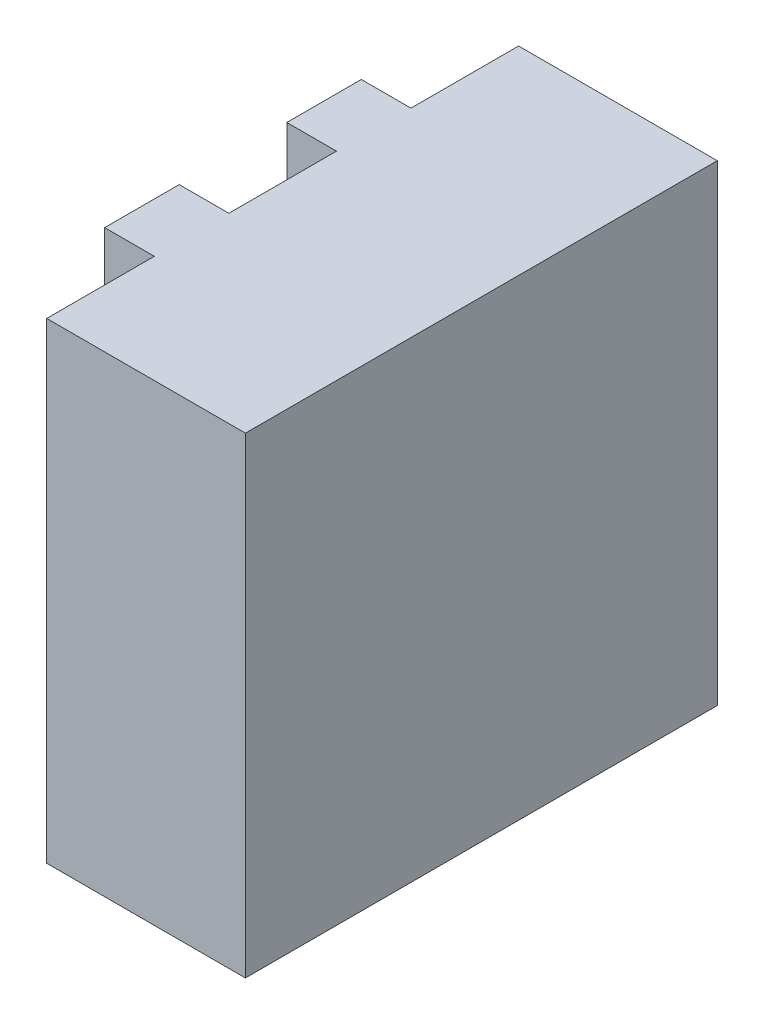
SolidWorks part; units mm, degrees
ref_plane "前视基准面" through (0, 0, 0) normal (0, 0, 1) x (1, 0, 0)
ref_plane "上视基准面" through (0, 0, 0) normal (0, 1, 0) x (1, 0, 0)
ref_plane "右视基准面" through (0, 0, 0) normal (1, 0, 0) x (0, 0, -1)
other "Configuration Table"
sketch "草图1" plane through (0, 0, 0) normal (1, 0, 0) x (0, 0, -1)
  line L0 (9.5, 7.7151) -> (7.3333, 7.7151) construction
  line L9 (0, 0) -> (9.5, 0)
  line L10 (0, 0) -> (0, 9.5)
  line L11 (0, 9.5) -> (9.5, 9.5)
  line L12 (9.5, 0) -> (9.5, 9.5)
  line L13 (7.3333, 9.5) -> (5.8333, 9.5)
  line L14 (7.3333, 9.5) -> (7.3333, 1.5)
  line L15 (7.3333, 1.5) -> (5.8333, 1.5)
  line L16 (5.8333, 9.5) -> (5.8333, 1.5)
  line L17 (3.6667, 9.5) -> (2.1667, 9.5)
  line L18 (3.6667, 9.5) -> (3.6667, 1.5)
  line L19 (3.6667, 1.5) -> (2.1667, 1.5)
  line L20 (2.1667, 9.5) -> (2.1667, 1.5)
  line L21 (5.8333, 7.7151) -> (3.6667, 7.7151) construction
  line L22 (2.1667, 7.7151) -> (0, 7.7151) construction
  line L23 (7.3333, 1.5) -> (7.3333, 0)
  line L24 (7.0833, 0.9) -> (6.0833, 0.9)
  line L25 (7.0833, 0.9) -> (7.0833, 0.6)
  line L26 (7.0833, 0.6) -> (6.0833, 0.6)
  line L27 (6.0833, 0.9) -> (6.0833, 0.6)
  line L28 (6.7333, 0.25) -> (6.4333, 0.25)
  line L29 (6.7333, 0.25) -> (6.7333, 1.25)
  line L30 (6.7333, 1.25) -> (6.4333, 1.25)
  line L31 (6.4333, 0.25) -> (6.4333, 1.25)
  line L33 (2.4167, 0.9) -> (3.4167, 0.9)
  line L34 (2.4167, 0.9) -> (2.4167, 0.6)
  line L35 (2.4167, 0.6) -> (3.4167, 0.6)
  line L36 (3.4167, 0.9) -> (3.4167, 0.6)
  point P28 (6.5833, 1.25)
  point P29 (6.5833, 1.5)
  point P30 (7.0833, 0.75)
  point P31 (6.7333, 0.75)
  point P32 (6.5833, 0.9)
  point P33 (7.3333, 0.75)
  point P39 (2.9167, 0.9)
  point P40 (2.9167, 1.5)
  point P41 (6.0833, 0.75)
  point P42 (3.4167, 0.75)
  dimension "D1" = 9.5
  dimension "D2" = 9.5
  dimension "D3" = 8
  dimension "D4" = 1.5
  dimension "D5" = 1
  dimension "D6" = 0.3
extrude "凸台-拉伸1" add sketch "草图1" along normal blind 4 contours L9 L12 L11 L10
extrude "凸台-拉伸2" add sketch "草图1<4>" against normal blind 1 contours L14 L15 L16 L13 | L18 L19 L20 L17
sketch "草图1<4>" plane through (0, 0, 0) normal (1, 0, 0) x (0, 0, -1) same geometry as "草图1"
extrude "切除-拉伸1" cut sketch "草图1<5>" along normal blind 0.2 contours L24 L27 L26 L25 | L29 L30 L31 L28 | L35 L36 L33 L34
sketch "草图1<5>" plane through (0, 0, 0) normal (1, 0, 0) x (0, 0, -1) same geometry as "草图1"
